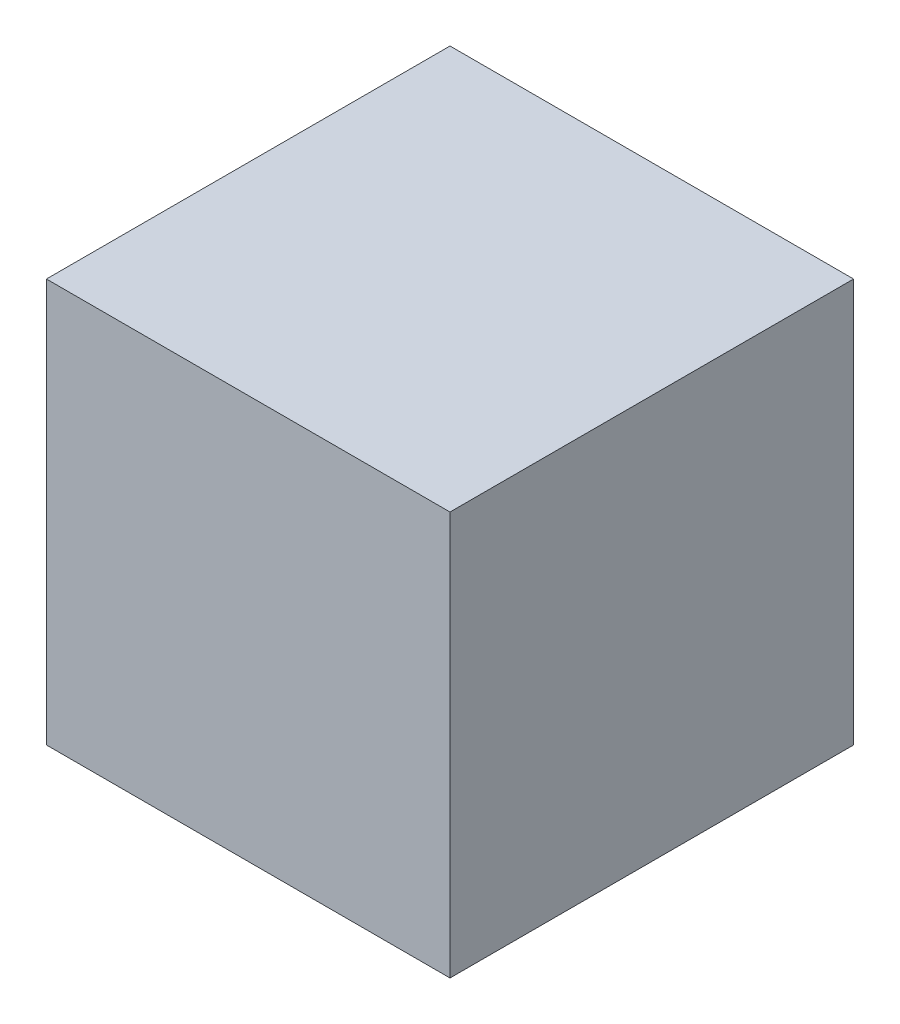
SolidWorks part; units mm, degrees
ref_plane "Front Plane" through (0, 0, 0) normal (0, 0, 1) x (1, 0, 0)
ref_plane "Top Plane" through (0, 0, 0) normal (0, 1, 0) x (1, 0, 0)
ref_plane "Right Plane" through (0, 0, 0) normal (1, 0, 0) x (0, 0, -1)
sketch "Sketch1" plane through (0, 0, 0) normal (0, 1, 0) x (1, 0, 0)
  line L1 (0, 0) -> (254, 0)
  line L2 (0, 0) -> (0, 254)
  line L3 (0, 254) -> (254, 254)
  line L4 (254, 0) -> (254, 254)
  dimension "D1" = 254
extrude "Boss-Extrude1" add sketch "Sketch1" along normal blind 254
